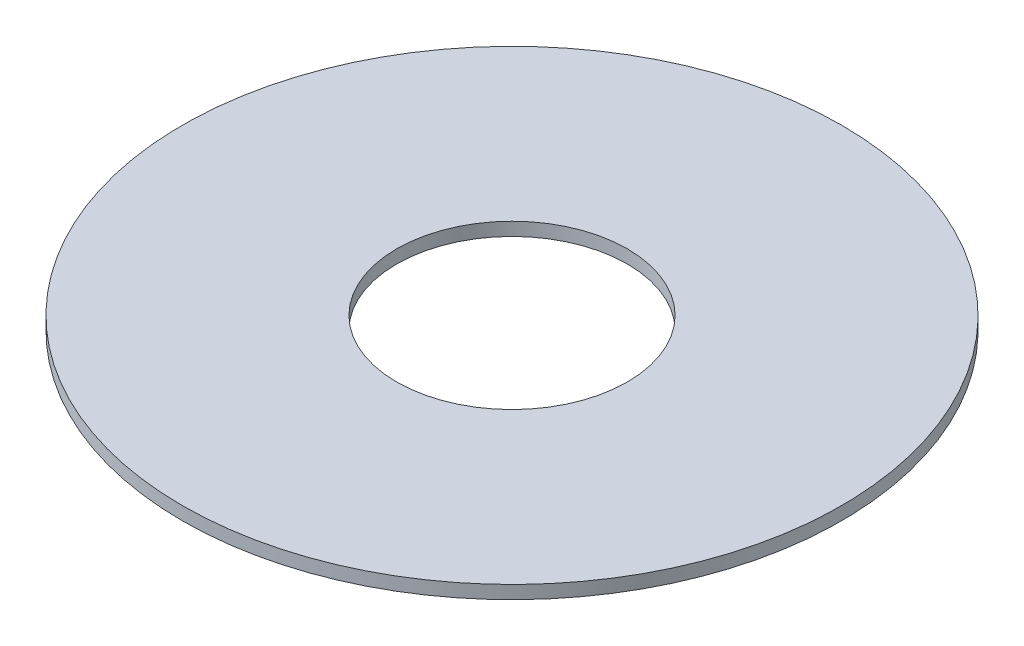
SolidWorks part; units mm, degrees
ref_plane "Front Plane" through (0, 0, 0) normal (0, 0, 1) x (1, 0, 0)
ref_plane "Top Plane" through (0, 0, 0) normal (0, 1, 0) x (1, 0, 0)
ref_plane "Right Plane" through (0, 0, 0) normal (1, 0, 0) x (0, 0, -1)
sketch "Sketch1" plane through (0, 0, 0) normal (0, 1, 0) x (1, 0, 0)
  circle A0 centre (0, 0) radius 100
  dimension "FLANGE_OD" = 200
extrude "Boss-Extrude1" add sketch "Sketch1" along normal blind 4
sketch "Sketch2" plane through (0, 0, 0) normal (0, 1, 0) x (1, 0, 0)
  circle A0 centre (0, 0) radius 35
  dimension "BORE_D" = 70
extrude "Cut-Extrude1" cut sketch "Sketch2" along normal through all
sketch "Sketch3" plane through (0, 4, 0) normal (0, 1, 0) x (1, 0, 0)
  circle A0 centre (0, 0) radius 28.6507 construction
  circle A1 centre (-28.6507, 0) radius 2.9867
  dimension "BOLT_D" = 5.9734
  dimension "BOLT_PCD" = 57.3014
extrude "Cut-Extrude2" cut sketch "Sketch3" against normal blind 2.8751 rebuild error yes
pattern_circular "CirPattern1" count 4 over 360 rebuild error yes
